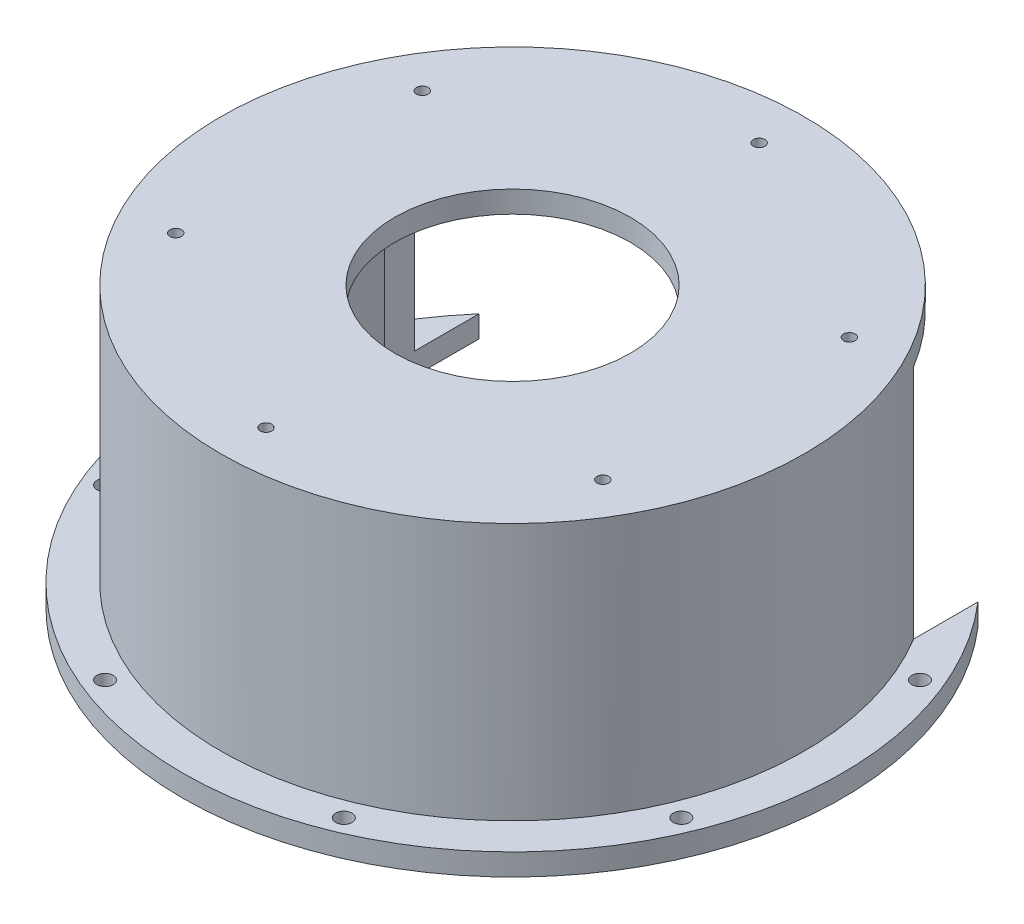
SolidWorks part; units mm, degrees
ref_plane "Front Plane" through (0, 0, 0) normal (0, 0, 1) x (1, 0, 0)
ref_plane "Top Plane" through (0, 0, 0) normal (0, 1, 0) x (1, 0, 0)
ref_plane "Right Plane" through (0, 0, 0) normal (1, 0, 0) x (0, 0, -1)
sketch "Sketch1" plane through (0, 0, 0) normal (0, 1, 0) x (1, 0, 0)
  circle A0 centre (0, 0) radius 144.4625
  dimension "D1" = 288.925
extrude "Boss-Extrude1" add sketch "Sketch1" along normal blind 9.525
sketch "Sketch2" plane through (0, 9.525, 0) normal (0, 1, 0) x (1, 0, 0)
  line L0 (0, 0) -> (-52.2459, 126.1327) construction
  line L2 (0, -5.2388) -> (0, 5.2388) construction
  circle A0 centre (0, 0) radius 136.525
  point P3 (-52.2459, 126.1327)
  point P4 (52.2459, 126.1327)
  point P5 (126.1327, 52.2459)
  point P8 (126.1327, -52.2459)
  point P9 (52.2459, -126.1327)
  point P10 (-52.2459, -126.1327)
  point P11 (-126.1327, -52.2459)
  point P12 (-126.1327, 52.2459)
  point P22 (0, 136.525)
  dimension "D1" = 273.05
  dimension "D3" = 22.5
  dimension "D4" = 22.5
  dimension "D2" = 8
hole_wizard "1/4 Clearance Hole1" positions "Sketch2" profile "Sketch3" hole size "1/4" standard "ANSI Inch" end condition up to next
sketch "Sketch3" plane through (0, 9.525, -136.525) normal (1, 0, 0) x (0, 0, 1)
  line L0 (0, 0) -> (0, 9.525)
  line L1 (0, 9.525) -> (3.5712, 9.525)
  line L2 (3.5712, 9.525) -> (3.5712, 0)
  line L5 (3.5712, 0) -> (0, 0)
  line L11 (0, -6.35) -> (0, 107.95) construction
  dimension "Thru Hole Dia." = 7.1425
  dimension "Thru Hole Depth" = 9.525
sketch "Sketch4" plane through (0, 9.525, 0) normal (0, 1, 0) x (1, 0, 0)
  circle A0 centre (0, 0) radius 127.7937
  circle A1 centre (0, 0) radius 121.4438
  dimension "D1" = 255.5875
  dimension "D2" = 242.8875
extrude "Boss-Extrude2" add sketch "Sketch4" along normal blind 112.7125
sketch "Sketch5" plane through (0, 122.2375, 0) normal (0, 1, 0) x (1, 0, 0)
  circle A0 centre (0, 0) radius 121.4438 construction
  circle A1 centre (0, 0) radius 127.7937
  circle A2 centre (0, 0) radius 127.7937
  circle A3 centre (0, 0) radius 121.4438
  dimension "D1" = 0
extrude "Boss-Extrude3" add sketch "Sketch5" against normal blind 9.525 contours A3
sketch "Sketch6" plane through (0, 0, 0) normal (0, -1, 0) x (1, 0, 0)
  circle A0 centre (0, 0) radius 121.4438
  dimension "D1" = 242.8875
extrude "Cut-Extrude1" cut sketch "Sketch6" against normal up to next
sketch "Sketch7" plane through (0, 122.2375, 0) normal (0, 1, 0) x (1, 0, 0)
  circle A0 centre (0, 0) radius 51.5938
  dimension "D1" = 103.1875
extrude "Cut-Extrude2" cut sketch "Sketch7" against normal up to next
sketch "Sketch10" plane through (0, 0, 0) normal (0, 1, 0) x (1, 0, 0)
  line L0 (-109.22, 53.0997) -> (109.22, 53.0997)
  line L1 (-109.22, 53.0997) -> (-109.22, 144.4625)
  line L2 (109.22, 53.0997) -> (109.22, 144.4625)
  line L3 (-109.22, 144.4625) -> (109.22, 144.4625)
  circle A0 centre (0, 0) radius 121.4438 construction
  circle A1 centre (0, 0) radius 144.4625 construction
  point P6 (0, 144.4625)
  dimension "D1" = 218.44
extrude "Cut-Extrude3" cut sketch "Sketch10" along normal up to surface (112.7125 mm away) contours L1 L3 L2 L0 up to face at (0, 112.7125, 51.5938)
sketch "Sketch11" plane through (0, 122.2375, 0) normal (0, 1, 0) x (1, 0, 0)
  circle A0 centre (0, 0) radius 107.95
  point P3 (0, -107.95)
  point P4 (-93.4874, -53.975)
  point P7 (-93.4874, 53.975)
  point P8 (0, 107.95)
  point P9 (93.4874, 53.975)
  point P10 (93.4874, -53.975)
  dimension "D1" = 215.9
  dimension "D2" = 6
hole_wizard "Tap Drill for 1/4-20 Tap1" positions "Sketch11" profile "Sketch12" hole size "1/4-20" standard "ANSI Inch" end condition up to next
sketch "Sketch12" plane through (93.4874, 122.2375, 53.975) normal (1, 0, 0) x (0, 0, 1)
  line L0 (0, 0) -> (0, 9.525)
  line L1 (0, 9.525) -> (2.5527, 9.525)
  line L2 (2.5527, 9.525) -> (2.5527, 0)
  line L5 (2.5527, 0) -> (0, 0)
  line L11 (0, -6.35) -> (0, 107.95) construction
  dimension "Thru Hole Dia." = 5.1054
  dimension "Thru Hole Depth" = 9.525
